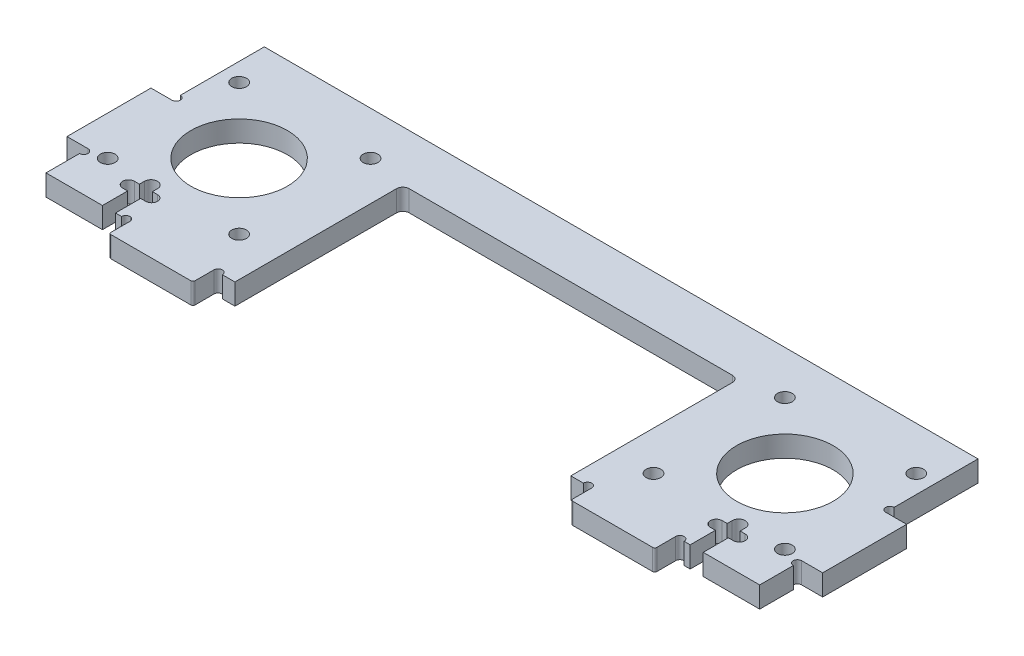
SolidWorks part; units mm, degrees
ref_plane "정면" through (0, 0, 0) normal (0, 0, 1) x (1, 0, 0)
ref_plane "윗면" through (0, 0, 0) normal (0, 1, 0) x (1, 0, 0)
ref_plane "우측면" through (0, 0, 0) normal (1, 0, 0) x (0, 0, -1)
sketch "스케치1" plane through (0, 0, 0) normal (0, 1, 0) x (1, 0, 0)
  line L1 (0, 0) -> (170, 0)
  line L2 (0, 0) -> (0, 52)
  line L3 (0, 52) -> (170, 52)
  line L4 (170, 0) -> (170, 52)
  dimension "D1" = 170
  dimension "D2" = 52
extrude "보스-돌출1" add sketch "스케치1" along normal blind 5
sketch "스케치2" plane through (0, 5, 0) normal (0, 1, 0) x (1, 0, 0)
  line L0 (85, 52) -> (85, 0) construction
  line L1 (170, 52) -> (0, 52) construction
  line L2 (0, 0) -> (170, 0) construction
  line L3 (150, 26) -> (20, 26) construction
  line L4 (134.35, 10.35) -> (165.65, 10.35) construction
  line L5 (134.35, 10.35) -> (134.35, 41.65) construction
  line L6 (134.35, 41.65) -> (165.65, 41.65) construction
  line L7 (165.65, 10.35) -> (165.65, 41.65) construction
  line L8 (134.35, 10.35) -> (165.65, 41.65) construction
  line L9 (134.35, 41.65) -> (165.65, 10.35) construction
  line L10 (170, 0) -> (170, 52) construction
  line L11 (35.65, 41.65) -> (4.35, 10.35) construction
  line L12 (35.65, 10.35) -> (4.35, 41.65) construction
  line L13 (4.35, 10.35) -> (4.35, 41.65) construction
  line L14 (35.65, 41.65) -> (4.35, 41.65) construction
  line L15 (35.65, 10.35) -> (35.65, 41.65) construction
  line L16 (35.65, 10.35) -> (4.35, 10.35) construction
  circle A0 centre (150, 26) radius 11.5
  circle A1 centre (165.65, 41.65) radius 1.75
  circle A2 centre (134.35, 41.65) radius 1.75
  circle A3 centre (165.65, 10.35) radius 1.75
  circle A4 centre (134.35, 10.35) radius 1.75
  circle A5 centre (35.65, 10.35) radius 1.75
  circle A6 centre (4.35, 10.35) radius 1.75
  circle A7 centre (35.65, 41.65) radius 1.75
  circle A8 centre (4.35, 41.65) radius 1.75
  circle A9 centre (20, 26) radius 11.5
  point P16 (170, 26)
  point P25 (85, 26)
  dimension "D1" = 23
  dimension "D3" = 3.5
  dimension "D2" = 31.3
  dimension "D4" = 20
extrude "컷-돌출1" cut sketch "스케치2" against normal blind 5
sketch "스케치3" plane through (0, 5, 0) normal (0, 1, 0) x (1, 0, 0)
  line L1 (0, 0) -> (170, 0) construction
  line L2 (130, 0) -> (150, 0)
  line L3 (130, 0) -> (130, -5)
  line L4 (130, -5) -> (150, -5)
  line L5 (150, 0) -> (150, -5)
  line L6 (130, -5) -> (40, -5) construction
  line L7 (20, 0) -> (40, 0)
  line L8 (20, 0) -> (20, -5)
  line L9 (20, -5) -> (40, -5)
  line L10 (40, 0) -> (40, -5)
  line L11 (150, -5) -> (170, -5) construction
  line L12 (170, -5) -> (170, 0) construction
  line L13 (0, 0) -> (0, -5) construction
  line L14 (0, -5) -> (20, -5) construction
  dimension "D1" = 20
  dimension "D2" = 20
  dimension "D3" = 5
extrude "보스-돌출2" add sketch "스케치3" against normal blind 5
sketch "스케치4" plane through (0, 5, 0) normal (0, 1, 0) x (1, 0, 0)
  line L0 (40, 0) -> (130, 0) construction
  line L1 (150, 0) -> (170, 0) construction
  line L2 (0, 0) -> (20, 0) construction
  circle A0 centre (129, 0) radius 1
  circle A1 centre (151, 0) radius 1
  circle A2 centre (19, 0) radius 1
  circle A3 centre (41, 0) radius 1
  dimension "D1" = 2
extrude "컷-돌출2" cut sketch "스케치4" against normal blind 5
sketch "스케치5" plane through (0, 5, 0) normal (0, 1, 0) x (1, 0, 0)
  line L0 (156.55, 0) -> (156.55, 6)
  line L1 (153.45, 10) -> (156.55, 10) construction
  line L2 (152.25, 6) -> (152.25, 8.8) construction
  line L3 (156.55, 6) -> (156.55, 8.8) construction
  line L4 (153.45, 0) -> (156.55, 0)
  line L5 (152.25, 8.8) -> (153.45, 8.8)
  line L6 (153.45, 0) -> (153.45, 6)
  line L7 (157.75, 8.8) -> (157.75, 6) construction
  line L8 (153.45, 6) -> (152.25, 6)
  line L9 (153.45, 8.8) -> (153.45, 6) construction
  line L10 (156.55, 8.8) -> (156.55, 10)
  line L11 (153.45, 6) -> (156.55, 6) construction
  line L12 (153.45, 8.8) -> (156.55, 8.8) construction
  line L13 (156.55, 8.8) -> (157.75, 8.8)
  line L14 (153.45, 8.8) -> (153.45, 10)
  line L15 (155, 10) -> (155, 12.1831) construction
  line L16 (157.75, 6) -> (156.55, 6)
  line L34 (170, 0) -> (170, 52) construction
  line L35 (85, 52) -> (85, 0) construction
  line L36 (170, 52) -> (0, 52) construction
  line L37 (42, 0) -> (128, 0) construction
  line L46 (15, 10) -> (15, 12.1831) construction
  line L47 (16.55, 8.8) -> (13.45, 8.8) construction
  line L48 (16.55, 6) -> (13.45, 6) construction
  line L49 (16.55, 8.8) -> (16.55, 6) construction
  line L50 (12.25, 8.8) -> (12.25, 6) construction
  line L51 (13.45, 6) -> (13.45, 8.8) construction
  line L52 (17.75, 6) -> (17.75, 8.8) construction
  line L53 (16.55, 10) -> (13.45, 10) construction
  line L63 (12.25, 6) -> (13.45, 6)
  line L64 (16.55, 8.8) -> (16.55, 10)
  line L65 (13.45, 8.8) -> (12.25, 8.8)
  line L66 (13.45, 8.8) -> (13.45, 10)
  line L67 (16.55, 6) -> (17.75, 6)
  line L68 (16.55, 0) -> (16.55, 6)
  line L69 (17.75, 8.8) -> (16.55, 8.8)
  line L70 (16.55, 0) -> (13.45, 0)
  line L71 (13.45, 0) -> (13.45, 6)
  arc A0 (156.55, 10) -> (153.45, 10) centre (155, 10) ccw
  arc A1 (152.25, 8.8) -> (152.25, 6) centre (152.25, 7.4) ccw
  arc A2 (157.75, 6) -> (157.75, 8.8) centre (157.75, 7.4) ccw
  arc A9 (12.25, 6) -> (12.25, 8.8) centre (12.25, 7.4) cw
  arc A10 (17.75, 8.8) -> (17.75, 6) centre (17.75, 7.4) cw
  arc A11 (13.45, 10) -> (16.55, 10) centre (15, 10) cw
  dimension "D1" = 3.1
  dimension "D2" = 10
  dimension "D3" = 5.5
  dimension "D4" = 2.8
  dimension "D12" = 15
extrude "컷-돌출3" cut sketch "스케치5" against normal blind 10
fillet "필렛1" radius 0.5 4 edges at (20, 2.5, 5) (130, 2.5, 5) (150, 2.5, 5) (40, 2.5, 5)
sketch "스케치6" plane through (0, 5, 0) normal (0, 1, 0) x (1, 0, 0)
  line L0 (85, 52) -> (85, 0) construction
  line L1 (170, 52) -> (0, 52) construction
  line L3 (85, 21) -> (85, 31) construction
  line L4 (81, 21) -> (81, 31)
  line L5 (89, 21) -> (89, 31)
  arc A0 (81, 21) -> (89, 21) centre (85, 21) ccw
  arc A1 (89, 31) -> (81, 31) centre (85, 31) ccw
  point P8 (85, 26)
  dimension "D1" = 4
  dimension "D2" = 10
extrude "컷-돌출4" [suppressed] cut sketch "스케치6" against normal blind 10
sketch "스케치7" plane through (0, 5, 0) normal (0, 1, 0) x (1, 0, 0)
  line L0 (170, 0) -> (170, 52) construction
  line L1 (170, 30) -> (175, 30)
  line L2 (170, 30) -> (170, 10)
  line L3 (170, 10) -> (175, 10)
  line L4 (175, 30) -> (175, 10)
  line L5 (0, 52) -> (0, 0) construction
  line L6 (0, 30) -> (-5, 30)
  line L7 (0, 30) -> (0, 10)
  line L8 (0, 10) -> (-5, 10)
  line L9 (-5, 30) -> (-5, 10)
  line L10 (156.55, 0) -> (170, 0) construction
  dimension "D1" = 5
  dimension "D2" = 10
  dimension "D3" = 20
extrude "보스-돌출3" add sketch "스케치7" against normal blind 5
sketch "스케치8" plane through (0, 5, 0) normal (0, 1, 0) x (1, 0, 0)
  line L0 (170, 0) -> (170, 10) construction
  line L1 (170, 30) -> (170, 52) construction
  line L2 (0, 10) -> (0, 0) construction
  line L3 (0, 52) -> (0, 30) construction
  circle A0 centre (170, 9) radius 1
  circle A1 centre (170, 31) radius 1
  circle A2 centre (0, 9) radius 1
  circle A3 centre (0, 31) radius 1
  dimension "D1" = 2
extrude "컷-돌출5" cut sketch "스케치8" against normal blind 5
sketch "스케치9" plane through (0, 5, 0) normal (0, 1, 0) x (1, 0, 0)
  line L0 (85, 52) -> (85, 0) construction
  line L1 (170, 52) -> (0, 52) construction
  line L2 (42, 0) -> (128, 0) construction
  line L4 (45, 40) -> (125, 40)
  line L5 (45, 40) -> (45, 0)
  line L6 (45, 0) -> (125, 0)
  line L7 (125, 40) -> (125, 0)
  line L8 (45, 40) -> (125, 0) construction
  line L9 (45, 0) -> (125, 40) construction
  point P6 (85, 20)
  dimension "D1" = 40
  dimension "D2" = 80
extrude "컷-돌출6" cut sketch "스케치9" against normal blind 10
fillet "필렛2" radius 1.5 2 edges at (125, 2.5, -40) (45, 2.5, -40)
